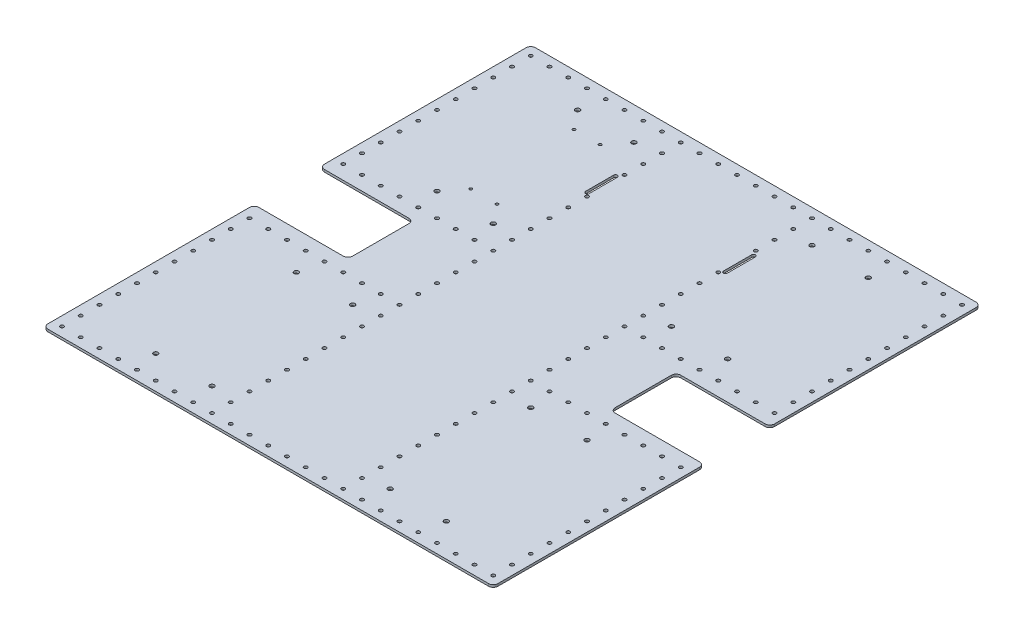
SolidWorks part; units mm, degrees
ref_plane "Front Plane" through (0, 0, 0) normal (0, 0, 1) x (1, 0, 0)
ref_plane "Top Plane" through (0, 0, 0) normal (0, 1, 0) x (1, 0, 0)
ref_plane "Right Plane" through (0, 0, 0) normal (1, 0, 0) x (0, 0, -1)
sketch "Sketch1" plane through (0, 0, 0) normal (0, 1, 0) x (1, 0, 0)
  line L1 (0, 0) -> (609.6, 0)
  line L2 (0, 0) -> (0, -660.4)
  line L3 (0, -660.4) -> (609.6, -660.4)
  line L4 (609.6, 0) -> (609.6, -660.4)
  line L5 (609.6, -285.75) -> (482.6, -285.75)
  line L6 (609.6, -285.75) -> (609.6, -374.65)
  line L7 (609.6, -374.65) -> (482.6, -374.65)
  line L8 (482.6, -285.75) -> (482.6, -374.65)
  line L9 (0, -285.75) -> (127, -285.75)
  line L10 (0, -285.75) -> (0, -374.65)
  line L11 (0, -374.65) -> (127, -374.65)
  line L12 (127, -285.75) -> (127, -374.65)
  dimension "D1" = 609.6
  dimension "D2" = 660.4
  dimension "D3" = 127
  dimension "D4" = 88.9
  dimension "D5" = 285.75
  dimension "D6" = 127
  dimension "D7" = 88.9
  dimension "D8" = 285.75
extrude "Boss-Extrude1" add sketch "Sketch1" along normal blind 3.175 contours L9 L12 L11 L2 L3 L4 L7 L8 L5 L1 region at (304.8, 0, 330.2)
sketch "Sketch2" plane through (0, 3.175, 0) normal (0, 1, 0) x (1, 0, 0)
  line L0 (0, 0) -> (0, -285.75) construction
  line L1 (0, -374.65) -> (0, -660.4) construction
  line L2 (0, -660.4) -> (609.6, -660.4) construction
  line L3 (0, 0) -> (609.6, 0) construction
  line L4 (0, -374.65) -> (0, -660.4) construction
  line L5 (0, -374.65) -> (127, -374.65) construction
  circle A452 centre (12.7, -647.7) radius 2.4
  circle A453 centre (38.1, -647.7) radius 2.4
  circle A454 centre (63.5, -647.7) radius 2.4
  circle A455 centre (88.9, -647.7) radius 2.4
  circle A456 centre (114.3, -647.7) radius 2.4
  circle A457 centre (139.7, -647.7) radius 2.4
  circle A458 centre (165.1, -647.7) radius 2.4
  circle A459 centre (190.5, -647.7) radius 2.4
  circle A460 centre (215.9, -647.7) radius 2.4
  circle A461 centre (241.3, -647.7) radius 2.4
  circle A462 centre (266.7, -647.7) radius 2.4
  circle A463 centre (292.1, -647.7) radius 2.4
  circle A464 centre (317.5, -647.7) radius 2.4
  circle A465 centre (342.9, -647.7) radius 2.4
  circle A466 centre (368.3, -647.7) radius 2.4
  circle A467 centre (393.7, -647.7) radius 2.4
  circle A468 centre (419.1, -647.7) radius 2.4
  circle A469 centre (444.5, -647.7) radius 2.4
  circle A470 centre (469.9, -647.7) radius 2.4
  circle A471 centre (495.3, -647.7) radius 2.4
  circle A472 centre (520.7, -647.7) radius 2.4
  circle A473 centre (546.1, -647.7) radius 2.4
  circle A474 centre (571.5, -647.7) radius 2.4
  circle A475 centre (596.9, -647.7) radius 2.4
  circle A476 centre (12.7, -622.3) radius 2.4
  circle A477 centre (12.7, -596.9) radius 2.4
  circle A478 centre (12.7, -571.5) radius 2.4
  circle A479 centre (12.7, -546.1) radius 2.4
  circle A480 centre (12.7, -520.7) radius 2.4
  circle A481 centre (12.7, -495.3) radius 2.4
  circle A482 centre (12.7, -469.9) radius 2.4
  circle A483 centre (12.7, -444.5) radius 2.4
  circle A484 centre (12.7, -419.1) radius 2.4
  circle A485 centre (12.7, -393.7) radius 2.4
  circle A486 centre (12.7, -622.3) radius 2.4
  circle A487 centre (596.9, -622.3) radius 2.4
  circle A488 centre (12.7, -596.9) radius 2.4
  circle A489 centre (596.9, -596.9) radius 2.4
  circle A490 centre (12.7, -571.5) radius 2.4
  circle A491 centre (596.9, -571.5) radius 2.4
  circle A492 centre (12.7, -546.1) radius 2.4
  circle A493 centre (596.9, -546.1) radius 2.4
  circle A494 centre (12.7, -520.7) radius 2.4
  circle A495 centre (596.9, -520.7) radius 2.4
  circle A496 centre (12.7, -495.3) radius 2.4
  circle A497 centre (596.9, -495.3) radius 2.4
  circle A498 centre (12.7, -469.9) radius 2.4
  circle A499 centre (596.9, -469.9) radius 2.4
  circle A500 centre (12.7, -444.5) radius 2.4
  circle A501 centre (596.9, -444.5) radius 2.4
  circle A502 centre (12.7, -419.1) radius 2.4
  circle A503 centre (596.9, -419.1) radius 2.4
  circle A504 centre (12.7, -393.7) radius 2.4
  circle A505 centre (596.9, -393.7) radius 2.4
  circle A506 centre (215.9, -622.3) radius 2.4
  circle A507 centre (393.7, -622.3) radius 2.4
  circle A508 centre (215.9, -596.9) radius 2.4
  circle A509 centre (393.7, -596.9) radius 2.4
  circle A510 centre (215.9, -571.5) radius 2.4
  circle A511 centre (393.7, -571.5) radius 2.4
  circle A512 centre (215.9, -546.1) radius 2.4
  circle A513 centre (393.7, -546.1) radius 2.4
  circle A514 centre (215.9, -520.7) radius 2.4
  circle A515 centre (393.7, -520.7) radius 2.4
  circle A516 centre (215.9, -495.3) radius 2.4
  circle A517 centre (393.7, -495.3) radius 2.4
  circle A518 centre (215.9, -469.9) radius 2.4
  circle A519 centre (393.7, -469.9) radius 2.4
  circle A520 centre (215.9, -444.5) radius 2.4
  circle A521 centre (393.7, -444.5) radius 2.4
  circle A522 centre (215.9, -419.1) radius 2.4
  circle A523 centre (393.7, -419.1) radius 2.4
  circle A524 centre (215.9, -393.7) radius 2.4
  circle A525 centre (393.7, -393.7) radius 2.4
  circle A526 centre (215.9, -368.3) radius 2.4
  circle A527 centre (393.7, -368.3) radius 2.4
  circle A528 centre (215.9, -342.9) radius 2.4
  circle A529 centre (393.7, -342.9) radius 2.4
  circle A530 centre (215.9, -317.5) radius 2.4
  circle A531 centre (393.7, -317.5) radius 2.4
  circle A532 centre (215.9, -292.1) radius 2.4
  circle A533 centre (393.7, -292.1) radius 2.4
  circle A534 centre (215.9, -266.7) radius 2.4
  circle A535 centre (393.7, -266.7) radius 2.4
  circle A536 centre (215.9, -241.3) radius 2.4
  circle A537 centre (393.7, -241.3) radius 2.4
  circle A538 centre (215.9, -215.9) radius 2.4
  circle A539 centre (393.7, -215.9) radius 2.4
  circle A540 centre (215.9, -190.5) radius 2.4
  circle A541 centre (393.7, -190.5) radius 2.4
  circle A542 centre (215.9, -165.1) radius 2.4
  circle A543 centre (393.7, -165.1) radius 2.4
  circle A544 centre (215.9, -139.7) radius 2.4
  circle A545 centre (393.7, -139.7) radius 2.4
  circle A546 centre (215.9, -114.3) radius 2.4
  circle A547 centre (393.7, -114.3) radius 2.4
  circle A548 centre (215.9, -88.9) radius 2.4
  circle A549 centre (393.7, -88.9) radius 2.4
  circle A550 centre (215.9, -63.5) radius 2.4
  circle A551 centre (393.7, -63.5) radius 2.4
  circle A552 centre (215.9, -38.1) radius 2.4
  circle A553 centre (393.7, -38.1) radius 2.4
  circle A554 centre (215.9, -12.7) radius 2.4
  circle A555 centre (393.7, -12.7) radius 2.4
  circle A556 centre (12.7, -12.7) radius 2.4
  circle A557 centre (38.1, -12.7) radius 2.4
  circle A558 centre (63.5, -12.7) radius 2.4
  circle A559 centre (88.9, -12.7) radius 2.4
  circle A560 centre (114.3, -12.7) radius 2.4
  circle A561 centre (139.7, -12.7) radius 2.4
  circle A562 centre (165.1, -12.7) radius 2.4
  circle A563 centre (190.5, -12.7) radius 2.4
  circle A564 centre (215.9, -12.7) radius 2.4
  circle A565 centre (241.3, -12.7) radius 2.4
  circle A566 centre (266.7, -12.7) radius 2.4
  circle A567 centre (292.1, -12.7) radius 2.4
  circle A568 centre (317.5, -12.7) radius 2.4
  circle A569 centre (342.9, -12.7) radius 2.4
  circle A570 centre (368.3, -12.7) radius 2.4
  circle A571 centre (393.7, -12.7) radius 2.4
  circle A572 centre (419.1, -12.7) radius 2.4
  circle A573 centre (444.5, -12.7) radius 2.4
  circle A574 centre (469.9, -12.7) radius 2.4
  circle A575 centre (495.3, -12.7) radius 2.4
  circle A576 centre (520.7, -12.7) radius 2.4
  circle A577 centre (546.1, -12.7) radius 2.4
  circle A578 centre (571.5, -12.7) radius 2.4
  circle A579 centre (596.9, -12.7) radius 2.4
  circle A580 centre (12.7, -38.1) radius 2.4
  circle A581 centre (12.7, -63.5) radius 2.4
  circle A582 centre (12.7, -88.9) radius 2.4
  circle A583 centre (12.7, -114.3) radius 2.4
  circle A584 centre (12.7, -139.7) radius 2.4
  circle A585 centre (12.7, -165.1) radius 2.4
  circle A586 centre (12.7, -190.5) radius 2.4
  circle A587 centre (12.7, -215.9) radius 2.4
  circle A588 centre (12.7, -241.3) radius 2.4
  circle A589 centre (12.7, -266.7) radius 2.4
  circle A590 centre (12.7, -38.1) radius 2.4
  circle A591 centre (596.9, -38.1) radius 2.4
  circle A592 centre (12.7, -63.5) radius 2.4
  circle A593 centre (596.9, -63.5) radius 2.4
  circle A594 centre (12.7, -88.9) radius 2.4
  circle A595 centre (596.9, -88.9) radius 2.4
  circle A596 centre (12.7, -114.3) radius 2.4
  circle A597 centre (596.9, -114.3) radius 2.4
  circle A598 centre (12.7, -139.7) radius 2.4
  circle A599 centre (596.9, -139.7) radius 2.4
  circle A600 centre (12.7, -165.1) radius 2.4
  circle A601 centre (596.9, -165.1) radius 2.4
  circle A602 centre (12.7, -190.5) radius 2.4
  circle A603 centre (596.9, -190.5) radius 2.4
  circle A604 centre (12.7, -215.9) radius 2.4
  circle A605 centre (596.9, -215.9) radius 2.4
  circle A606 centre (12.7, -241.3) radius 2.4
  circle A607 centre (596.9, -241.3) radius 2.4
  circle A608 centre (12.7, -266.7) radius 2.4
  circle A609 centre (596.9, -266.7) radius 2.4
  dimension "D3" = 12.7
  dimension "D4" = 24
  dimension "D5" = 11
  dimension "D6" = 11
  dimension "D7" = 26
  dimension "D8" = 4.8
  dimension "D1" = 4.8
  dimension "D9" = 12.7
  dimension "D11" = 24
  dimension "D2" = 12.7
  dimension "D10" = 12.7
  dimension "D12" = 11
  dimension "D13" = 11
extrude "Cut-Extrude1" cut sketch "Sketch2" against normal blind 119.634
sketch "Sketch3" plane through (0, 3.175, 0) normal (0, 1, 0) x (1, 0, 0)
  line L0 (609.6, -393.7) -> (0, -393.7)
  line L1 (304.8, -660.4) -> (304.8, 0)
  line L2 (609.6, -374.65) -> (609.6, -660.4) construction
  line L3 (0, -374.65) -> (0, -660.4) construction
  line L4 (609.6, -374.65) -> (482.6, -374.65) construction
  line L5 (0, -660.4) -> (609.6, -660.4) construction
  line L6 (0, 0) -> (609.6, 0) construction
  line L7 (127, -330.2) -> (482.6, -330.2)
  line L8 (127, -285.75) -> (127, -374.65) construction
  line L9 (482.6, -285.75) -> (482.6, -374.65) construction
  circle A0 centre (546.1, -393.7) radius 2.425
  circle A1 centre (571.5, -393.7) radius 2.425
  circle A2 centre (520.7, -393.7) radius 2.425
  circle A3 centre (495.3, -393.7) radius 2.425
  circle A4 centre (469.9, -393.7) radius 2.425
  circle A5 centre (444.5, -393.7) radius 2.425
  circle A6 centre (419.1, -393.7) radius 2.425
  circle A7 centre (190.5, -393.7) radius 2.425
  circle A8 centre (165.1, -393.7) radius 2.425
  circle A9 centre (139.7, -393.7) radius 2.425
  circle A10 centre (114.3, -393.7) radius 2.425
  circle A11 centre (88.9, -393.7) radius 2.425
  circle A12 centre (38.1, -393.7) radius 2.425
  circle A13 centre (63.5, -393.7) radius 2.425
  circle A14 centre (63.5, -266.7) radius 2.425
  circle A15 centre (38.1, -266.7) radius 2.425
  circle A16 centre (88.9, -266.7) radius 2.425
  circle A17 centre (114.3, -266.7) radius 2.425
  circle A18 centre (139.7, -266.7) radius 2.425
  circle A19 centre (165.1, -266.7) radius 2.425
  circle A20 centre (190.5, -266.7) radius 2.425
  circle A21 centre (419.1, -266.7) radius 2.425
  circle A22 centre (444.5, -266.7) radius 2.425
  circle A23 centre (469.9, -266.7) radius 2.425
  circle A24 centre (495.3, -266.7) radius 2.425
  circle A25 centre (520.7, -266.7) radius 2.425
  circle A26 centre (571.5, -266.7) radius 2.425
  circle A27 centre (546.1, -266.7) radius 2.425
  dimension "D2" = 4.85
  dimension "D3" = 38.1
  dimension "D4" = 7
  dimension "D1" = 19.05
extrude "Cut-Extrude2" cut sketch "Sketch3" against normal through all contours A7 L0 | A7 L0 | A8 L0 | A8 L0 | A9 L0 | A9 L0 | A10 L0 | A10 L0 | A11 L0 | A11 L0 | A12 L0 | A12 L0 | L0 A6 | L0 A6 | L0 A5 | L0 A5 | L0 A4 | L0 A4 | L0 A3 | L0 A3 | L0 A2 | L0 A2 | L0 A0 | L0 A0 | L0 A1 | L0 A1 | A13 L0 | A13 L0 region at (571.5, 3.175, 394.7292) region at (571.5, 3.175, 392.6708) region at (38.1, 3.175, 394.7292) region at (38.1, 3.175, 392.6708) region at (63.5, 3.175, 394.7292) region at (63.5, 3.175, 392.6708) region at (88.9, 3.175, 394.7292) region at (88.9, 3.175, 392.6708) region at (114.3, 3.175, 394.7292) region at (114.3, 3.175, 392.6708) region at (139.7, 3.175, 394.7292) region at (139.7, 3.175, 392.6708) region at (165.1, 3.175, 394.7292) region at (165.1, 3.175, 392.6708) region at (190.5, 3.175, 394.7292) region at (190.5, 3.175, 392.6708) region at (419.1, 3.175, 394.7292) region at (419.1, 3.175, 392.6708) region at (444.5, 3.175, 394.7292) region at (444.5, 3.175, 392.6708) region at (469.9, 3.175, 394.7292) region at (469.9, 3.175, 392.6708) region at (495.3, 3.175, 394.7292) region at (495.3, 3.175, 392.6708) region at (520.7, 3.175, 394.7292) region at (520.7, 3.175, 392.6708) region at (546.1, 3.175, 394.7292) region at (546.1, 3.175, 392.6708)
extrude "Cut-Extrude3" cut sketch "Sketch3<3>" against normal through all contours A15 | A14 | A16 | A17 | A18 | A19 | A20 | A21 | A22 | A24 | A23 | A25 | A27 | A26 | A21 | A22 region at (63.5, 3.175, 266.7) region at (38.1, 3.175, 266.7) region at (88.9, 3.175, 266.7) region at (114.3, 3.175, 266.7) region at (139.7, 3.175, 266.7) region at (165.1, 3.175, 266.7) region at (190.5, 3.175, 266.7) region at (419.1, 3.175, 266.7) region at (444.5, 3.175, 266.7) region at (469.9, 3.175, 266.7) region at (495.3, 3.175, 266.7) region at (520.7, 3.175, 266.7) region at (571.5, 3.175, 266.7) region at (546.1, 3.175, 266.7)
sketch "Sketch3<3>" plane through (0, 3.175, 0) normal (0, 1, 0) x (1, 0, 0) same geometry as "Sketch3"
sketch "Sketch4" plane through (0, 3.175, 0) normal (0, 1, 0) x (1, 0, 0)
  line L0 (0, 0) -> (609.6, 0) construction
  line L5 (425.45, -44.45) -> (501.65, -44.45)
  line L6 (425.45, -44.45) -> (425.45, -234.95)
  line L7 (425.45, -234.95) -> (501.65, -234.95)
  line L8 (501.65, -44.45) -> (501.65, -234.95)
  line L9 (609.6, 0) -> (609.6, -285.75) construction
  line L10 (609.6, -285.75) -> (482.6, -285.75) construction
  line L11 (304.8, 0) -> (304.8, -660.4)
  line L12 (0, -660.4) -> (609.6, -660.4) construction
  line L13 (127, -330.2) -> (482.6, -330.2)
  line L14 (127, -285.75) -> (127, -374.65) construction
  line L15 (482.6, -285.75) -> (482.6, -374.65) construction
  line L16 (107.95, -44.45) -> (107.95, -234.95)
  line L17 (184.15, -234.95) -> (107.95, -234.95)
  line L18 (184.15, -44.45) -> (184.15, -234.95)
  line L19 (184.15, -44.45) -> (107.95, -44.45)
  line L20 (184.15, -615.95) -> (107.95, -615.95)
  line L21 (184.15, -615.95) -> (184.15, -425.45)
  line L22 (184.15, -425.45) -> (107.95, -425.45)
  line L23 (107.95, -615.95) -> (107.95, -425.45)
  line L24 (501.65, -615.95) -> (501.65, -425.45)
  line L25 (425.45, -425.45) -> (501.65, -425.45)
  line L26 (425.45, -615.95) -> (425.45, -425.45)
  line L27 (425.45, -615.95) -> (501.65, -615.95)
  circle A18 centre (425.45, -44.45) radius 3.1
  circle A19 centre (501.65, -44.45) radius 3.1
  circle A20 centre (501.65, -234.95) radius 3.0934
  circle A21 centre (425.45, -234.95) radius 3.1
  circle A22 centre (184.15, -234.95) radius 3.1
  circle A23 centre (107.95, -234.95) radius 3.0934
  circle A24 centre (107.95, -44.45) radius 3.1
  circle A25 centre (184.15, -44.45) radius 3.1
  circle A26 centre (184.15, -615.95) radius 3.1
  circle A27 centre (107.95, -615.95) radius 3.1
  circle A28 centre (107.95, -425.45) radius 3.0934
  circle A29 centre (184.15, -425.45) radius 3.1
  circle A30 centre (425.45, -425.45) radius 3.1
  circle A31 centre (501.65, -425.45) radius 3.0934
  circle A32 centre (501.65, -615.95) radius 3.1
  circle A33 centre (425.45, -615.95) radius 3.1
  circle A34 centre (147.8513, -125.3052) radius 21.4946
  dimension "D1" = 76.2
  dimension "D2" = 190.5
  dimension "D6" = 6.2
  dimension "D7" = 6.2
  dimension "D8" = 6.1867
  dimension "D9" = 6.2
  dimension "D3" = 44.45
  dimension "D4" = 107.95
  dimension "D5" = 50.8
extrude "Cut-Extrude4" cut sketch "Sketch4" against normal through all contours A24 L16 L19 | A24 L19 L16 | A25 L19 L18 | A25 L18 L19 | A22 L18 L17 | A22 L17 L18 | A23 L16 L17 | A23 L17 L16 | L7 A20 L8 | L8 A20 L7 | L7 A21 L6 | L6 A21 L7 | L8 A19 L5 | L5 A19 L8 | L5 A18 L6 | L6 A18 L5 | A31 L24 L25 | A31 L25 L24 | A30 L25 L26 | A30 L26 L25 | A32 L24 L27 | A32 L27 L24 | A33 L26 L27 | A33 L27 L26 | L20 A26 L21 | L21 A26 L20 | L20 A27 L23 | L23 A27 L20 | L22 A29 L21 | L21 A29 L22 | L23 A28 L22 | L22 A28 L23 | A31 region at (425.0114, 3.175, 44.0114) region at (426.7657, 3.175, 45.7657) region at (502.0886, 3.175, 44.0114) region at (500.3343, 3.175, 45.7657) region at (426.7657, 3.175, 233.6343) region at (425.0114, 3.175, 235.3886) region at (502.0876, 3.175, 235.3876) region at (500.3371, 3.175, 233.6371) region at (109.2657, 3.175, 45.7657) region at (107.5114, 3.175, 44.0114) region at (109.2629, 3.175, 233.6371) region at (107.5124, 3.175, 235.3876) region at (184.5886, 3.175, 44.0114) region at (182.8343, 3.175, 45.7657) region at (182.8343, 3.175, 233.6343) region at (184.5886, 3.175, 235.3886) region at (107.5114, 3.175, 616.3886) region at (109.2657, 3.175, 614.6343) region at (182.8343, 3.175, 614.6343) region at (184.5886, 3.175, 616.3886) region at (107.5124, 3.175, 425.0124) region at (109.2629, 3.175, 426.7629) region at (182.8343, 3.175, 426.7657) region at (184.5886, 3.175, 425.0114) region at (500.3343, 3.175, 614.6343) region at (502.0886, 3.175, 616.3886) region at (500.3371, 3.175, 426.7629) region at (502.0876, 3.175, 425.0124) region at (425.0114, 3.175, 616.3886) region at (426.7657, 3.175, 614.6343) region at (426.7657, 3.175, 426.7657) region at (425.0114, 3.175, 425.0114)
fillet "Fillet1" radius 6.35 12 edges at (0, 1.5875, 285.75) (609.6, 1.5875, 0) (609.6, 1.5875, 285.75) (482.6, 1.5875, 285.75) (482.6, 1.5875, 374.65) (609.6, 1.5875, 374.65) (609.6, 1.5875, 660.4) (0, 1.5875, 660.4) (0, 1.5875, 374.65) (127, 1.5875, 374.65) (127, 1.5875, 285.75) (0, 1.5875, 0)
sketch "Sketch5" plane through (0, 3.175, 0) normal (0, 1, 0) x (1, 0, 0)
  line L1 (128.27, -69.85) -> (163.83, -69.85)
  line L2 (128.27, -69.85) -> (128.27, -209.55)
  line L3 (128.27, -209.55) -> (163.83, -209.55)
  line L4 (163.83, -69.85) -> (163.83, -209.55)
  circle A0 centre (107.95, -44.45) radius 3.1 construction
  circle A1 centre (128.27, -69.85) radius 1.905
  circle A2 centre (163.83, -69.85) radius 1.905
  circle A3 centre (163.83, -209.55) radius 1.905
  circle A4 centre (128.27, -209.55) radius 1.905
  dimension "D4" = 20.32
  dimension "D5" = 3.81
  dimension "D6" = 3.81
  dimension "D7" = 3.81
  dimension "D8" = 3.81
  dimension "D1" = 35.56
  dimension "D2" = 139.7
  dimension "D3" = 25.4
extrude "Cut-Extrude5" cut sketch "Sketch5" against normal through all contours L1 A1 L2 | L2 A1 L1 | L4 A2 L1 | L1 A2 L4 | L3 A3 L4 | L4 A3 L3 | L3 A4 L2 | L2 A4 L3 region at (128.0005, 3.175, 69.5805) region at (129.0785, 3.175, 70.6585) region at (164.0995, 3.175, 69.5805) region at (163.0215, 3.175, 70.6585) region at (129.0785, 3.175, 208.7415) region at (128.0005, 3.175, 209.8195) region at (164.0995, 3.175, 209.8195) region at (163.0215, 3.175, 208.7415)
sketch "Sketch6" plane through (0, 3.175, 0) normal (0, 1, 0) x (1, 0, 0)
  line L0 (213.5, -88.9) -> (218.3, -88.9)
  line L1 (215.9, -86.5) -> (215.9, -91.3)
  line L2 (211.328, -96.52) -> (211.328, -134.62) construction
  line L3 (215.9, -88.9) -> (211.328, -88.9)
  line L4 (215.9, -88.9) -> (215.9, -96.52)
  line L5 (215.9, -96.52) -> (211.328, -96.52)
  line L6 (211.328, -88.9) -> (211.328, -96.52)
  line L7 (213.868, -96.52) -> (213.868, -134.62)
  line L8 (208.788, -96.52) -> (208.788, -134.62)
  line L9 (304.8, 0) -> (304.8, -129.3666)
  line L10 (6.35, 0) -> (603.25, 0) construction
  line L11 (398.272, -96.52) -> (398.272, -134.62) construction
  line L12 (395.732, -96.52) -> (395.732, -134.62)
  line L13 (400.812, -96.52) -> (400.812, -134.62)
  line L14 (398.272, -88.9) -> (398.272, -96.52)
  line L15 (393.7, -96.52) -> (398.272, -96.52)
  line L16 (393.7, -88.9) -> (393.7, -96.52)
  line L17 (393.7, -88.9) -> (398.272, -88.9)
  line L18 (393.7, -86.5) -> (393.7, -91.3)
  line L19 (396.1, -88.9) -> (391.3, -88.9)
  circle A0 centre (215.9, -88.9) radius 2.4 construction
  arc A1 (213.868, -96.52) -> (208.788, -96.52) centre (211.328, -96.52) ccw
  arc A2 (208.788, -134.62) -> (213.868, -134.62) centre (211.328, -134.62) ccw
  circle A3 centre (215.9, -114.3) radius 2.4
  arc A4 (395.732, -96.52) -> (400.812, -96.52) centre (398.272, -96.52) cw
  arc A5 (400.812, -134.62) -> (395.732, -134.62) centre (398.272, -134.62) cw
  circle A6 centre (393.7, -114.3) radius 2.4
  point P11 (211.328, -115.57)
  point P26 (398.272, -115.57)
  dimension "D1" = 4.572
  dimension "D2" = 7.62
  dimension "D3" = 38.1
  dimension "D4" = 5.08
extrude "Cut-Extrude6" cut sketch "Sketch6" against normal through all contours L5 A1 L6 | A3 L7 L5 L6 A1 L8 A2 | A4 L15 L14 | L12 A6 A5 L13 A4 L14 L15 region at (212.406, 3.175, 95.442) region at (211.2944, 3.175, 116.064) region at (398.3056, 3.175, 116.064) region at (397.194, 3.175, 95.442)
extrude "Boss-Extrude2" add sketch "Sketch6<3>" against normal blind 3.175 contours L7 A3 | A6 L12 region at (215.9795, 3.175, 114.3) region at (393.6205, 3.175, 114.3)
sketch "Sketch6<3>" plane through (0, 3.175, 0) normal (0, 1, 0) x (1, 0, 0) same geometry as "Sketch6"
